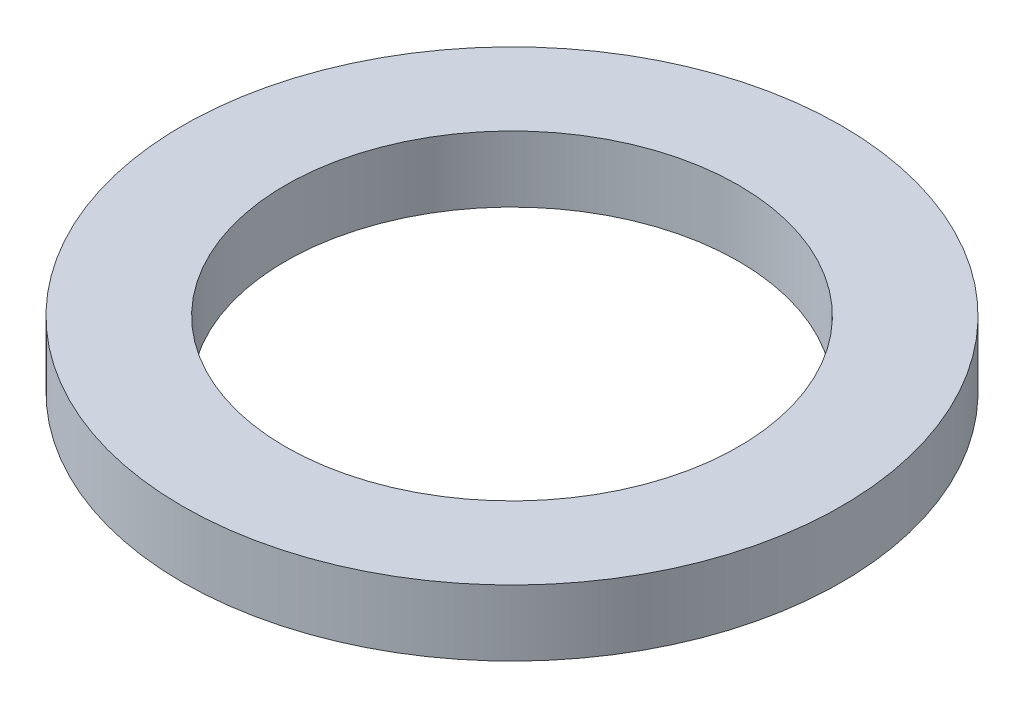
SolidWorks part; units mm, degrees
ref_plane "Front Plane" through (0, 0, 0) normal (0, 0, 1) x (1, 0, 0)
ref_plane "Top Plane" through (0, 0, 0) normal (0, 1, 0) x (1, 0, 0)
ref_plane "Right Plane" through (0, 0, 0) normal (1, 0, 0) x (0, 0, -1)
sketch "Sketch1" plane through (0, 0, 0) normal (0, 1, 0) x (1, 0, 0)
  circle A0 centre (0, 0) radius 40
  dimension "FLANGE_OD" = 80
extrude "Boss-Extrude1" add sketch "Sketch1" along normal blind 8
sketch "Sketch2" plane through (0, 0, 0) normal (0, 1, 0) x (1, 0, 0)
  circle A0 centre (0, 0) radius 27.5
  dimension "BORE_D" = 55
extrude "Cut-Extrude1" cut sketch "Sketch2" along normal through all
sketch "Sketch3" plane through (0, 8, 0) normal (0, 1, 0) x (1, 0, 0)
  circle A0 centre (0, 0) radius 16.6929 construction
  circle A1 centre (-16.6929, 0) radius 1.7577
  dimension "BOLT_D" = 3.5155
  dimension "BOLT_PCD" = 33.3858
extrude "Cut-Extrude2" cut sketch "Sketch3" against normal blind 7.4709 rebuild error yes
pattern_circular "CirPattern1" count 8 over 360 rebuild error yes
